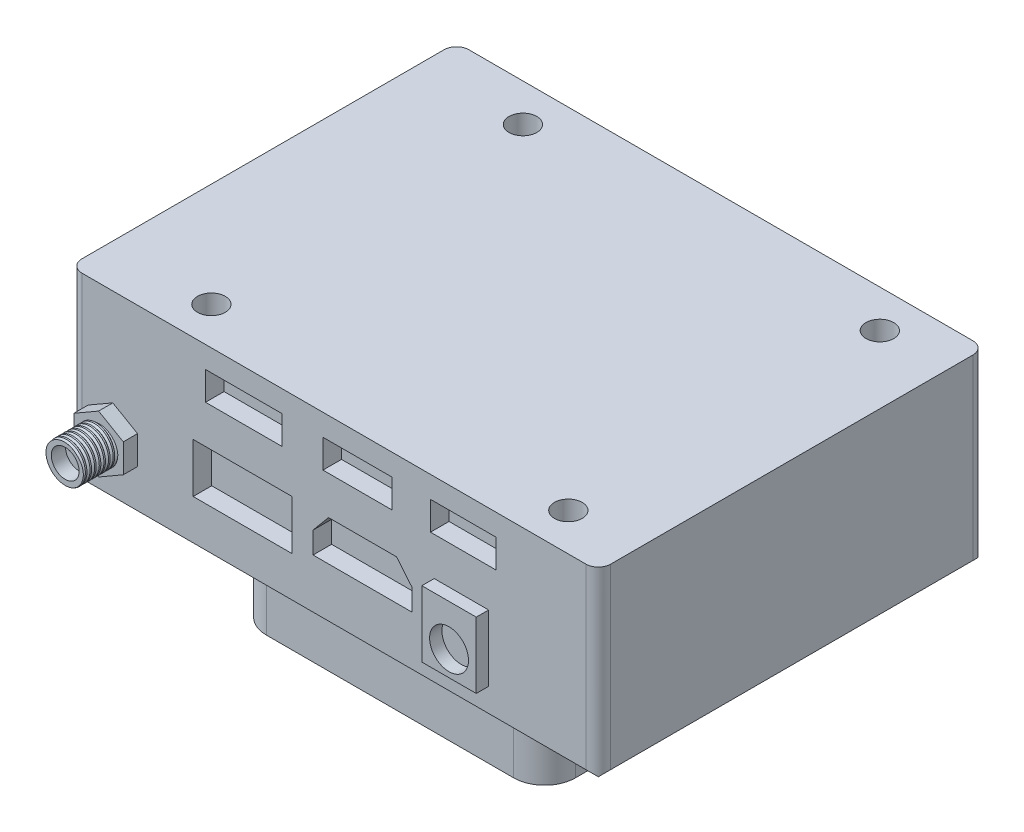
SolidWorks part; units mm, degrees
material "6061 Alloy"
ref_plane "Front Plane" through (0, 0, 0) normal (0, 0, 1) x (1, 0, 0)
ref_plane "Top Plane" through (0, 0, 0) normal (0, 1, 0) x (1, 0, 0)
ref_plane "Right Plane" through (0, 0, 0) normal (1, 0, 0) x (0, 0, -1)
sketch "Sketch1" plane through (0, 0, 0) normal (0, 1, 0) x (1, 0, 0)
  line L1 (-42.775, 31.3) -> (42.775, 31.3)
  line L2 (-42.775, 31.3) -> (-42.775, -31.3)
  line L3 (-42.775, -31.3) -> (42.775, -31.3)
  line L4 (42.775, 31.3) -> (42.775, -31.3)
  line L5 (-42.775, 31.3) -> (42.775, -31.3) construction
  line L6 (-42.775, -31.3) -> (42.775, 31.3) construction
  point P0 (0, 0)
  dimension "D1" = 62.6
  dimension "D2" = 85.55
extrude "Boss-Extrude1" add sketch "Sketch1" along normal blind 31.5
sketch "Sketch2" plane through (0, 31.5, 0) normal (0, 1, 0) x (1, 0, 0)
  line L0 (-42.775, 31.3) -> (-42.775, -31.3) construction
  line L1 (-25.925, 25.2) -> (-25.925, -25.2) construction
  circle A0 centre (-25.925, 25.2) radius 2.25
  circle A1 centre (31.825, 25.2) radius 2.25
  circle A2 centre (31.825, -25.2) radius 2.25
  circle A3 centre (-25.925, -25.2) radius 2.25
  dimension "D1" = 4.5
  dimension "D2" = 16.85
  dimension "D3" = 50.4
  dimension "D4" = 25.2
  dimension "D5" = 57.75
extrude "Cut-Extrude1" cut sketch "Sketch2" against normal blind 31.5
sketch "Sketch3" plane through (0, 0, 31.3) normal (0, 0, 1) x (1, 0, 0)
  line L0 (-42.775, 31.5) -> (-42.775, 0) construction
  line L1 (-22.775, 17.2) -> (-6.775, 17.2)
  line L2 (-22.775, 17.2) -> (-22.775, 9.2)
  line L3 (-22.775, 9.2) -> (-6.775, 9.2)
  line L4 (-6.775, 17.2) -> (-6.775, 9.2)
  line L5 (-20.775, 28) -> (-8.375, 28)
  line L6 (-20.775, 28) -> (-20.775, 23.4)
  line L7 (-20.775, 23.4) -> (-8.375, 23.4)
  line L8 (-8.375, 28) -> (-8.375, 23.4)
  line L9 (-3.375, 10.7) -> (-3.375, 14.2)
  line L10 (-3.375, 14.2) -> (-0.8746, 17.2)
  line L11 (-0.8746, 17.2) -> (10.1254, 17.2)
  line L12 (10.1254, 17.2) -> (12.625, 14.2)
  line L13 (12.625, 14.2) -> (12.625, 10.7)
  line L14 (12.625, 10.7) -> (-3.375, 10.7)
  line L15 (-42.775, 31.5) -> (42.775, 31.5) construction
  line L17 (-1.775, 28) -> (9.425, 28)
  line L18 (-1.775, 28) -> (-1.775, 23.4)
  line L19 (-1.775, 23.4) -> (9.425, 23.4)
  line L20 (9.425, 28) -> (9.425, 23.4)
  line L21 (15.625, 28) -> (26.225, 28)
  line L22 (15.625, 28) -> (15.625, 23.4)
  line L23 (15.625, 23.4) -> (26.225, 23.4)
  line L24 (26.225, 28) -> (26.225, 23.4)
  dimension "D1" = 8
  dimension "D2" = 16
  dimension "D3" = 4.6
  dimension "D4" = 12.4
  dimension "D5" = 22
  dimension "D6" = 11
  dimension "D7" = 16
  dimension "D8" = 3
  dimension "D9" = 6.5
  dimension "D10" = 3
  dimension "D11" = 3.5
  dimension "D12" = 4.6
  dimension "D13" = 11.2
  dimension "D14" = 6.6
  dimension "D15" = 4.6
  dimension "D16" = 10.6
  dimension "D17" = 6.2
  dimension "D18" = 6.2
  dimension "D19" = 3.4
  dimension "D20" = 20
  dimension "D21" = 50.19
extrude "Cut-Extrude2" cut sketch "Sketch3" against normal blind 3
sketch "Sketch4" plane through (0, 0, 31.3) normal (0, 0, 1) x (1, 0, 0)
  line L0 (10.1254, 17.2) -> (-0.8746, 17.2) construction
  line L1 (16.225, 17.2) -> (25.025, 17.2)
  line L2 (16.225, 17.2) -> (16.225, 6.5)
  line L3 (16.225, 6.5) -> (25.025, 6.5)
  line L4 (25.025, 17.2) -> (25.025, 6.5)
  line L5 (12.625, 10.7) -> (12.625, 14.2) construction
  circle A0 centre (20.625, 10.5) radius 3.15
  dimension "D1" = 6.3
  dimension "D2" = 10.7
  dimension "D3" = 8.8
  dimension "D4" = 3.6
  dimension "D5" = 4
  dimension "D6" = 4.4
extrude "Boss-Extrude2" add sketch "Sketch4" along normal blind 2
sketch "Sketch5" plane through (0, 0, 31.3) normal (0, 0, 1) x (1, 0, 0)
  line L0 (-6.775, 17.2) -> (-22.775, 17.2) construction
  line L1 (-35.775, 6.5812) -> (-31.775, 8.8906)
  line L2 (-31.775, 8.8906) -> (-31.775, 13.5094)
  line L3 (-31.775, 13.5094) -> (-35.775, 15.8188)
  line L4 (-35.775, 15.8188) -> (-39.775, 13.5094)
  line L5 (-39.775, 13.5094) -> (-39.775, 8.8906)
  line L6 (-39.775, 8.8906) -> (-35.775, 6.5812)
  line L7 (-42.775, 31.5) -> (-42.775, 0) construction
  circle A0 centre (-35.775, 11.2) radius 4 construction
  dimension "D1" = 8
  dimension "D2" = 6
  dimension "D3" = 11
extrude "Boss-Extrude3" add sketch "Sketch5" along normal blind 2.3
sketch "Sketch6" plane through (0, 0, 33.6) normal (0, 0, 1) x (1, 0, 0)
  line L0 (-39.775, 13.5094) -> (-31.775, 8.8906) construction
  circle A0 centre (-35.775, 11.2) radius 3.11
  dimension "D1" = 6.22
extrude "Boss-Extrude4" add sketch "Sketch6" along normal blind 5.4
ref_plane "Plane1" through (0, 11.2, 0) normal (0, 1, 0) x (1, 0, 0)
sketch "Sketch7" plane through (0, 0, 33.6) normal (0, 0, 1) x (1, 0, 0)
  circle A1 centre (-35.775, 11.2) radius 3.11
  circle A2 centre (-35.775, 11.2) radius 3.11
  dimension "D1" = 0
curve "Helix/Spiral1" pitch 0.75 height 6.75 turns 9
sketch "Sketch10" plane through (0, 11.2, 0) normal (0, 1, 0) x (1, 0, 0)
  line L0 (-32.665, -33.6) -> (-32.665, -34.1)
  line L2 (-32.665, -34.1) -> (-32.965, -33.85)
  line L3 (-32.965, -33.85) -> (-32.665, -33.6)
  line L7 (-38.885, -33.6) -> (-32.665, -33.6) construction
  line L8 (-32.665, -39) -> (-32.665, -33.6) construction
  dimension "D1" = 0.5
  dimension "D2" = 0.3
sweep "Cut-Sweep1" cut profiles "Sketch10" path "Helix/Spiral1"
sketch "Sketch13" plane through (0, 0, 39) normal (0, 0, 1) x (1, 0, 0)
  line L0 (-39.775, 13.5094) -> (-31.775, 8.8906) construction
  circle A0 centre (-35.775, 11.2) radius 2.25
  dimension "D1" = 4.5
extrude "Cut-Extrude3" cut sketch "Sketch13" against normal blind 2.3
mirror "Mirror1" about plane through (0, 0, 0) normal (0, 0, 1) of "Boss-Extrude4", "Cut-Extrude3", "Cut-Sweep1", "Boss-Extrude3"
sketch "Sketch14" plane through (0, 0, 0) normal (0, -1, 0) x (1, 0, 0)
  line L0 (-16.975, 19.75) -> (22.525, 19.75) construction
  line L1 (22.525, 19.75) -> (22.525, -19.75) construction
  line L2 (22.525, -19.75) -> (-16.975, -19.75) construction
  line L3 (-16.975, -19.75) -> (-16.975, 19.75) construction
  line L4 (-36.175, 18) -> (-36.175, 24.7)
  line L5 (-36.175, 24.7) -> (-17.975, 24.7)
  line L6 (36.175, 24.7) -> (36.175, 19.5)
  line L7 (36.175, 19.5) -> (32.475, 19.5)
  line L8 (29.475, 16.5) -> (29.475, -16.5)
  line L9 (32.475, -19.5) -> (36.175, -19.5)
  line L10 (36.175, -19.5) -> (36.175, -24.7)
  line L11 (36.175, -24.7) -> (23.525, -24.7)
  line L12 (-36.175, -24.7) -> (-36.175, -18)
  line L13 (-36.175, -18) -> (-29.875, -18)
  line L14 (-26.875, -15) -> (-26.875, 15)
  line L15 (-29.875, 18) -> (-36.175, 18)
  line L16 (-36.175, 16.5) -> (-36.175, 0.6)
  line L17 (-36.175, 0.6) -> (-28.875, 0.6)
  line L18 (-28.875, 0.6) -> (-28.875, 13.5)
  line L19 (-31.875, 16.5) -> (-36.175, 16.5)
  line L20 (-42.775, -31.3) -> (-42.775, 31.3) construction
  line L21 (-17.975, 22.9996) -> (-17.975, 24.7)
  line L22 (-15.975, 22.9996) -> (-15.975, 24.7)
  line L23 (-15.975, 24.7) -> (21.525, 24.7)
  line L24 (21.525, 22.9996) -> (21.525, 24.7)
  line L25 (23.525, 22.9996) -> (23.525, 24.7)
  line L26 (23.525, 24.7) -> (36.175, 24.7)
  line L27 (21.525, -22.9996) -> (21.525, -24.7)
  line L28 (23.525, -24.7) -> (23.525, -22.9996)
  line L29 (21.525, -24.7) -> (-15.975, -24.7)
  line L30 (-17.975, -22.9996) -> (-17.975, -24.7)
  line L31 (-15.975, -24.7) -> (-15.975, -22.9996)
  line L32 (-17.975, -24.7) -> (-36.175, -24.7)
  line L33 (-42.775, 31.3) -> (42.775, 31.3) construction
  line L34 (42.775, -31.3) -> (-42.775, -31.3) construction
  line L35 (-36.175, -0.6) -> (-36.175, -16.5)
  line L36 (-36.175, -16.5) -> (-31.875, -16.5)
  line L37 (-28.875, -13.5) -> (-28.875, -0.6)
  line L38 (-28.875, -0.6) -> (-36.175, -0.6)
  line L39 (36.175, 18) -> (33.975, 18)
  line L40 (30.975, 15) -> (30.975, 0.6)
  line L41 (30.975, 0.6) -> (36.175, 0.6)
  line L42 (36.175, 0.6) -> (36.175, 18)
  line L43 (36.175, -18) -> (33.975, -18)
  line L44 (30.975, -15) -> (30.975, -0.6)
  line L45 (30.975, -0.6) -> (36.175, -0.6)
  line L46 (36.175, -0.6) -> (36.175, -18)
  arc A0 (-17.975, 22.9996) -> (-15.975, 22.9996) centre (-16.975, 19.75) ccw
  arc A1 (-15.975, -22.9996) -> (-17.975, -22.9996) centre (-16.975, -19.75) ccw
  arc A2 (23.525, -22.9996) -> (21.525, -22.9996) centre (22.525, -19.75) ccw
  arc A3 (21.525, 22.9996) -> (23.525, 22.9996) centre (22.525, 19.75) ccw
  arc A4 (32.475, 19.5) -> (29.475, 16.5) centre (32.475, 16.5) ccw
  arc A5 (29.475, -16.5) -> (32.475, -19.5) centre (32.475, -16.5) ccw
  arc A6 (-29.875, -18) -> (-26.875, -15) centre (-29.875, -15) ccw
  arc A7 (-26.875, 15) -> (-29.875, 18) centre (-29.875, 15) ccw
  arc A8 (-28.875, 13.5) -> (-31.875, 16.5) centre (-31.875, 13.5) ccw
  arc A9 (-31.875, -16.5) -> (-28.875, -13.5) centre (-31.875, -13.5) ccw
  arc A10 (33.975, 18) -> (30.975, 15) centre (33.975, 15) ccw
  arc A11 (33.975, -18) -> (30.975, -15) centre (33.975, -15) cw
  dimension "D1" = 6.8
  dimension "D2" = 39.5
  dimension "D4" = 72.35
  dimension "D6" = 1.5
  dimension "D10" = 25.8
  dimension "D11" = 3
  dimension "D12" = 2.5
  dimension "D24" = 1.2
  dimension "D26" = 3
  dimension "D27" = 36
  dimension "D29" = 1.5
  dimension "D32" = 3
  dimension "D33" = 3
  dimension "D36" = 6.7
  dimension "D3" = 39.5
  dimension "D5" = 36
  dimension "D7" = 6.6
  dimension "D8" = 2
  dimension "D9" = 9.3
  dimension "D13" = 15.9
  dimension "D14" = 2
  dimension "D15" = 1
  dimension "D16" = 2
  dimension "D17" = 1
  dimension "D18" = 2
  dimension "D19" = 1
  dimension "D20" = 2
  dimension "D21" = 1
  dimension "D22" = 6.6
  dimension "D23" = 6.6
  dimension "D25" = 1.5
  dimension "D28" = 1.2
  dimension "D30" = 2.2
  dimension "D31" = 1.5
  dimension "D34" = 5.2
  dimension "D35" = 1.5
  dimension "D37" = 1.7004
  dimension "D38" = 17.4
  dimension "D39" = 5.2
extrude "Cut-Extrude5" cut sketch "Sketch14" against normal blind 2.7
chamfer "Chamfer1" distance 2.7 angle 45 10 edges at (-20.8531, 2.7, 24.7) (26.5781, 2.7, -24.7) (-32.1469, 2.7, -24.7) (-16.975, 2.7, -16.35) (2.775, 2.7, -24.7) (22.525, 2.7, -16.35) (26.5781, 2.7, 24.7) (22.525, 2.7, 16.35) (2.775, 2.7, 24.7) (-16.975, 2.7, 16.35)
chamfer "Chamfer3" distance 2.7 angle 45 16 edges at (34.325, 2.7, -19.5) (34.325, 2.7, 19.5) (30.3537, 2.7, -18.6213) (30.3537, 2.7, 18.6213) (29.475, 2.7, 0) (-36.175, 2.7, -20) (-36.175, 2.7, 20) (-33.025, 2.7, 18) (-33.025, 2.7, -18) (-27.7537, 2.7, 17.1213) (-27.7537, 2.7, -17.1213) (-26.875, 2.7, 0) (42.775, 0, 0) (0, 0, -31.3) (-42.775, 0, 0) (0, 0, 31.3)
sketch "Sketch15" plane through (0, 0, 0) normal (0, -1, 0) x (1, 0, 0)
  circle A0 centre (-16.975, 19.75) radius 1.75
  arc A1 (-17.975, 22.9996) -> (-15.975, 22.9996) centre (-16.975, 19.75) ccw construction
  circle A3 centre (22.525, 19.75) radius 1.75
  circle A4 centre (-16.975, -19.75) radius 1.75
  circle A5 centre (22.525, -19.75) radius 1.75
  dimension "D1" = 3.5
extrude "Cut-Extrude6" cut sketch "Sketch15" against normal blind 3
sketch "Sketch17" plane through (0, 0, 0) normal (0, -1, 0) x (-1, 0, 0)
  line L1 (17.22, -25) -> (-22.78, -25)
  line L2 (22.22, -20) -> (22.22, 20)
  line L3 (17.22, 25) -> (-22.78, 25)
  line L4 (-27.78, -20) -> (-27.78, 20)
  circle A0 centre (16.975, -19.75) radius 3
  circle A1 centre (-22.525, -19.75) radius 3
  circle A2 centre (16.975, 19.75) radius 3
  circle A3 centre (-22.525, 19.75) radius 3
  arc A4 (-22.78, -25) -> (-27.78, -20) centre (-22.78, -20) cw
  arc A5 (-22.78, 25) -> (-27.78, 20) centre (-22.78, 20) ccw
  arc A6 (22.22, 20) -> (17.22, 25) centre (17.22, 20) ccw
  arc A7 (17.22, -25) -> (22.22, -20) centre (17.22, -20) ccw
  circle A8 centre (-2.78, 0) radius 23.875
  point P18 (-27.78, -25)
  point P25 (22.22, -25)
  dimension "D1" = 6
  dimension "D2" = 5
  dimension "D3" = 50
  dimension "D4" = 47.75
  dimension "D5" = 50
  dimension "D6" = 2.78
  dimension "D7" = 25
  dimension "D8" = 25
extrude "Boss-Extrude5" add sketch "Sketch17" along normal blind 10.6
sketch "Sketch18" plane through (0, 0, 0) normal (0, -1, 0) x (1, 0, 0)
  line L0 (0.28, 4.3301) -> (0.28, 25)
  line L1 (0.28, 25) -> (5.28, 25)
  line L2 (5.28, 25) -> (5.28, 4.3301)
  line L3 (5.28, -4.3301) -> (23.1806, -14.6651)
  line L4 (23.1806, -14.6651) -> (25.6806, -10.3349)
  line L5 (25.6806, -10.3349) -> (7.78, 0)
  line L6 (2.78, 0) -> (2.78, 25) construction
  line L7 (24.4306, -12.5) -> (2.78, 0) construction
  line L8 (0.28, -4.3301) -> (-17.6206, -14.6651)
  line L9 (-17.6206, -14.6651) -> (-20.1206, -10.3349)
  line L10 (-20.1206, -10.3349) -> (-2.22, 0)
  line L11 (-18.8706, -12.5) -> (2.78, 0) construction
  arc A0 (0.28, 4.3301) -> (-2.22, 0) centre (2.78, 0) ccw
  arc A1 (7.78, 0) -> (5.28, 4.3301) centre (2.78, 0) ccw
  arc A2 (0.28, -4.3301) -> (5.28, -4.3301) centre (2.78, 0) ccw
  dimension "D1" = 10
  dimension "D2" = 5
  dimension "D3" = 2.5
  dimension "D4" = 25
  dimension "D5" = 20.6699
  dimension "D6" = 5
  dimension "D7" = 2.5
  dimension "D8" = 25
  dimension "D9" = 120
  dimension "D10" = 5
  dimension "D11" = 2.5
  dimension "D12" = 25
  dimension "D13" = 120
  dimension "D14" = 2.78
extrude "Boss-Extrude6" add sketch "Sketch18" along normal blind 2
sketch "Sketch21" plane through (-42.775, 0, 0) normal (-1, 0, 0) x (0, 0, 1)
  line L0 (31.3, 31.5) -> (31.3, 2.7) construction
  line L1 (10.1, 27.9) -> (21.8, 27.9)
  line L2 (10.1, 27.9) -> (10.1, 23.2)
  line L3 (10.1, 23.2) -> (21.8, 23.2)
  line L4 (21.8, 27.9) -> (21.8, 23.2)
  line L5 (-31.3, 31.5) -> (31.3, 31.5) construction
  line L7 (6.6, 27.9) -> (-2.7, 27.9)
  line L8 (6.6, 27.9) -> (6.6, 23.2)
  line L9 (6.6, 23.2) -> (-2.7, 23.2)
  line L10 (-2.7, 27.9) -> (-2.7, 23.2)
  line L11 (-5.3, 27.9) -> (-18, 27.9)
  line L12 (-5.3, 27.9) -> (-5.3, 25.9)
  line L13 (-5.3, 25.9) -> (-18, 25.9)
  line L14 (-18, 27.9) -> (-18, 25.9)
  dimension "D1" = 4.7
  dimension "D2" = 11.7
  dimension "D3" = 9.5
  dimension "D4" = 3.6
  dimension "D5" = 4.7
  dimension "D6" = 9.3
  dimension "D7" = 3.5
  dimension "D8" = 2
  dimension "D9" = 12.7
  dimension "D10" = 2.6
extrude "Cut-Extrude7" cut sketch "Sketch21" against normal blind 3
sketch "Sketch22" plane through (0, 0, -31.3) normal (0, 0, -1) x (-1, 0, 0)
  line L0 (-42.775, 31.5) -> (42.775, 31.5) construction
  line L1 (-28.175, 28) -> (-17.475, 28)
  line L2 (-28.175, 28) -> (-28.175, 23.6)
  line L3 (-28.175, 23.6) -> (-17.475, 23.6)
  line L4 (-17.475, 28) -> (-17.475, 23.6)
  line L5 (-14.675, 28) -> (-6.575, 28)
  line L6 (-14.675, 28) -> (-14.675, 23.6)
  line L7 (-14.675, 23.6) -> (-6.575, 23.6)
  line L8 (-6.575, 28) -> (-6.575, 23.6)
  line L9 (-42.775, 31.5) -> (-42.775, 2.7) construction
  line L10 (-26.325, 12.25) -> (-9.525, 12.25) construction
  line L11 (6.725, 12.25) -> (23.525, 12.25) construction
  line L12 (-26.325, 14.1) -> (-9.525, 14.1)
  line L13 (-26.325, 10.4) -> (-9.525, 10.4)
  line L15 (6.725, 14.1) -> (23.525, 14.1)
  line L16 (6.725, 10.4) -> (23.525, 10.4)
  arc A0 (-26.325, 14.1) -> (-26.325, 10.4) centre (-26.325, 12.25) ccw
  arc A1 (-9.525, 10.4) -> (-9.525, 14.1) centre (-9.525, 12.25) ccw
  arc A2 (6.725, 14.1) -> (6.725, 10.4) centre (6.725, 12.25) ccw
  arc A3 (23.525, 10.4) -> (23.525, 14.1) centre (23.525, 12.25) ccw
  point P16 (-17.925, 12.25)
  point P23 (15.125, 12.25)
  dimension "D8" = 16.8
  dimension "D10" = 17.4
  dimension "D11" = 16.25
  dimension "D1" = 4.4
  dimension "D2" = 10.7
  dimension "D3" = 4.4
  dimension "D4" = 8.1
  dimension "D5" = 3.5
  dimension "D6" = 2.8
  dimension "D7" = 14.6
  dimension "D9" = 3.7
extrude "Cut-Extrude8" cut sketch "Sketch22" against normal blind 3
fillet "Fillet1" radius 2 4 edges at (42.775, 17.1, -31.3) (42.775, 17.1, 31.3) (-42.775, 17.1, 31.3) (-42.775, 17.1, -31.3)
